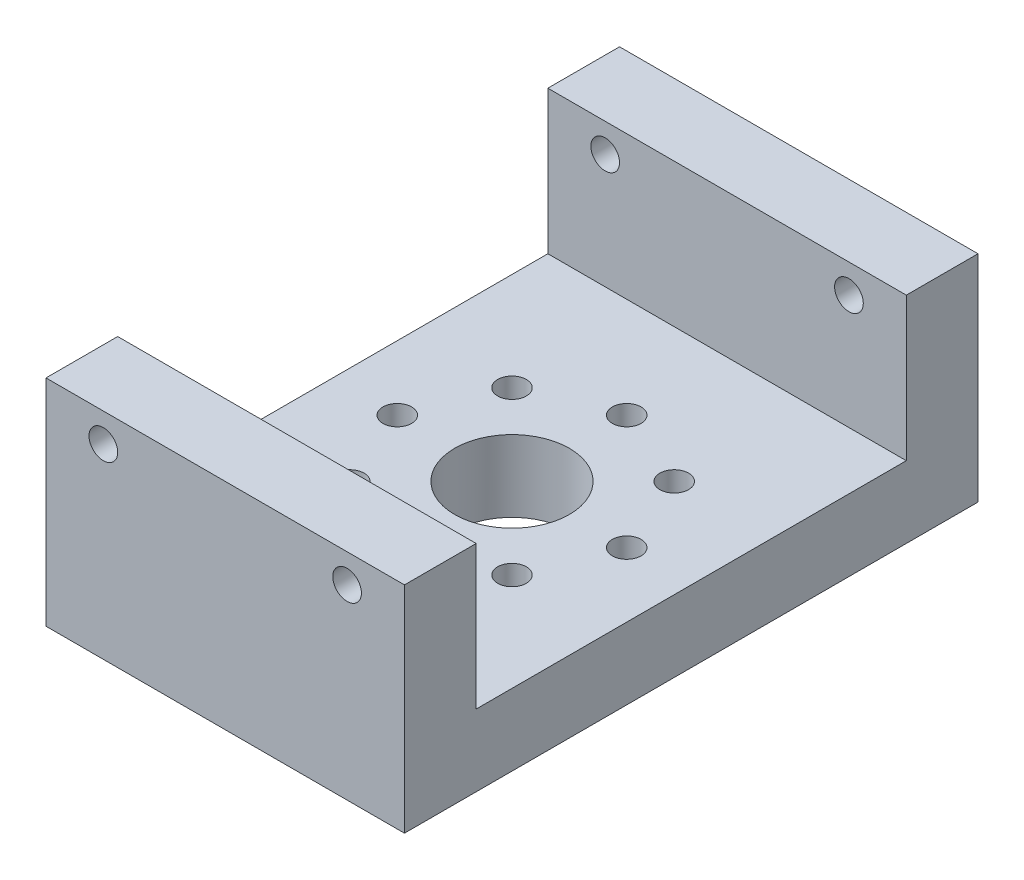
SolidWorks part; units mm, degrees
material "1060 Alloy"
ref_plane "Front Plane" through (0, 0, 0) normal (0, 0, 1) x (1, 0, 0)
ref_plane "Top Plane" through (0, 0, 0) normal (0, 1, 0) x (1, 0, 0)
ref_plane "Right Plane" through (0, 0, 0) normal (1, 0, 0) x (0, 0, -1)
sketch "Sketch1" plane through (0, 0, 0) normal (0, 1, 0) x (1, 0, 0)
  line L1 (-12.5, 20) -> (12.5, 20)
  line L2 (-12.5, 20) -> (-12.5, -20)
  line L3 (-12.5, -20) -> (12.5, -20)
  line L4 (12.5, 20) -> (12.5, -20)
  line L5 (-12.5, 20) -> (12.5, -20) construction
  line L6 (-12.5, -20) -> (12.5, 20) construction
  point P0 (0, 0)
  dimension "D1" = 40
  dimension "D2" = 25
extrude "Boss-Extrude1" add sketch "Sketch1" along normal blind 5
sketch "Sketch2" [suppressed] plane through (0, 5, 0) normal (0, 1, 0) x (1, 0, 0)
  line L0 (-5, 0) -> (5, 0) construction
  circle A0 centre (-5, 0) radius 1
  circle A1 centre (5, 0) radius 1
  point P4 (0, 0)
  dimension "D2" = 2
  dimension "D3" = 2
  dimension "D1" = 10
extrude "Cut-Extrude1" [suppressed] cut sketch "Sketch2" against normal through all
sketch "Sketch3" [suppressed] plane through (0, 5, 0) normal (0, 1, 0) x (1, 0, 0)
  circle A0 centre (-5, 0) radius 2
  circle A1 centre (5, 0) radius 2
  dimension "D1" = 4
  dimension "D2" = 4
extrude "Cut-Extrude2" [suppressed] cut sketch "Sketch3" against normal blind 2
sketch "Sketch5" plane through (0, 5, 0) normal (0, 1, 0) x (1, 0, 0)
  line L0 (12.5, -20) -> (12.5, 20) construction
  line L1 (-12.5, 20) -> (12.5, 20)
  line L2 (-12.5, 20) -> (-12.5, 15)
  line L3 (-12.5, 15) -> (12.5, 15)
  line L4 (12.5, 20) -> (12.5, 15)
  line L5 (0, 15) -> (0, -15) construction
  line L6 (-12.5, -20) -> (12.5, -20)
  line L7 (-12.5, -20) -> (-12.5, -15)
  line L8 (-12.5, -15) -> (12.5, -15)
  line L9 (12.5, -20) -> (12.5, -15)
  point P14 (0, 0)
  dimension "D1" = 30
extrude "Boss-Extrude2" add sketch "Sketch5" along normal blind 10
sketch "Sketch6" plane through (0, 0, 20) normal (0, 0, 1) x (1, 0, 0)
  line L0 (-8.5, 13) -> (8.5, 13) construction
  line L1 (0, 0) -> (0, 15) construction
  line L2 (-12.5, 15) -> (12.5, 15) construction
  circle A0 centre (-8.5, 13) radius 1
  circle A1 centre (8.5, 13) radius 1
  point P10 (0, 13)
  dimension "D1" = 2
  dimension "D2" = 2
  dimension "D3" = 17
  dimension "D4" = 2
extrude "Cut-Extrude3" cut sketch "Sketch6" against normal through all
sketch "Sketch7" plane through (0, 0, 0) normal (0, -1, 0) x (1, 0, 0)
  circle A0 centre (0, 0) radius 4
  circle A1 centre (0, 0) radius 8
  circle A2 centre (0, 8) radius 1
  circle A3 centre (5.6569, 5.6569) radius 1
  circle A4 centre (8, 0) radius 1
  circle A5 centre (5.6569, -5.6569) radius 1
  circle A6 centre (0, -8) radius 1
  circle A7 centre (-5.6569, -5.6569) radius 1
  circle A8 centre (-8, 0) radius 1
  circle A9 centre (-5.6569, 5.6569) radius 1
  point P6 (-0.0045, -8.6966)
  point P7 (0, -8)
  point P8 (8, 0)
  point P23 (0, 0)
  dimension "D1" = 8
  dimension "D2" = 16
  dimension "D3" = 2
  dimension "D4" = 8
extrude "Cut-Extrude4" cut sketch "Sketch7" against normal blind 10 contours A1 A2 | A1 A2 | A1 A3 | A1 A3 | A1 A4 | A1 A4 | A1 A5 | A1 A5 | A1 A6 | A1 A6 | A1 A7 | A1 A7 | A1 A8 | A1 A8 | A1 A9 | A1 A9 | A0 region at (0, 0, 0) region at (7.5645, 0, 0) region at (8.413, 0, 0) region at (5.3489, 0, 5.3489) region at (5.9489, 0, 5.9489) region at (5.9489, 0, -5.9489) region at (5.3489, 0, -5.3489) region at (0, 0, 7.5645) region at (0, 0, 8.413) region at (0, 0, -8.413) region at (0, 0, -7.5645) region at (-5.3489, 0, 5.3489) region at (-5.9489, 0, 5.9489) region at (-5.9489, 0, -5.9489) region at (-5.3489, 0, -5.3489) region at (-7.5645, 0, 0) region at (-8.413, 0, 0)
